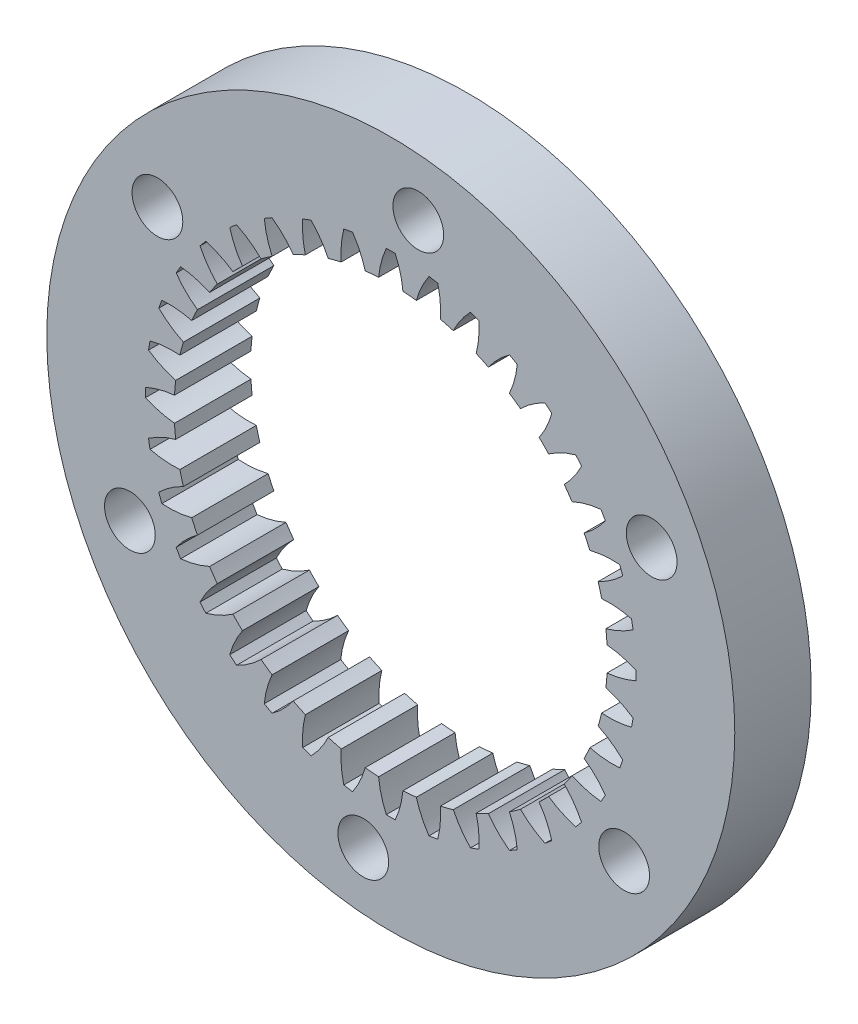
SolidWorks part; units mm, degrees
material "AISI 1020"
ref_plane "Front" through (0, 0, 0) normal (0, 0, 1) x (1, 0, 0)
ref_plane "Top" through (0, 0, 0) normal (0, 1, 0) x (1, 0, 0)
ref_plane "Right" through (0, 0, 0) normal (1, 0, 0) x (0, 0, -1)
sketch "Sketch2" plane through (0, 0, 0) normal (1, 0, 0) x (0, 0, -1)
  line L0 (0, 0) -> (-125.1835, 0) construction
  line L1 (-125.1835, 0) -> (0, 0) construction
ref_axis "Axis1" through (0, 0, -80.9) along (0, 0, 1)
sketch "gearSketch" plane through (0, 0, 0) normal (0, 0, 1) x (1, 0, 0)
  circle A0 centre (0, 0) radius 28.575
  dimension "bodyOD" = 57.15
extrude "gearBody" add sketch "gearSketch" along normal blind 6.35
sketch "boreSketch" plane through (0, 0, 0) normal (0, 0, -1) x (-1, 0, 0)
  circle A0 centre (0, 0) radius 17.9917
  dimension "minorDiameterBore" = 35.9833
extrude "bodyBore" cut sketch "boreSketch" against normal through all
sketch "toothCut1" plane through (-279.4, 0, 0) normal (0, 0, -1) x (-1, 0, 0)
  line L0 (-280.2309, 19.0319) -> (-272.8842, 17.2539) construction
  line L1 (-279.4, 0) -> (-279.4, 19.05) construction
  line L2 (-279.4, 0) -> (-280.2309, 19.0319) construction
  line L3 (-279.4, 279.4) -> (-279.4, 0) construction
  line L4 (-279.4, 0) -> (-280.4097, 17.9633)
  line L5 (-279.4, 0) -> (-278.3903, 17.9633)
  circle A0 centre (-279.4, 0) radius 17.9917 construction
  circle A1 centre (-279.4, 0) radius 18.4432 construction
  circle A2 centre (-279.4, 0) radius 19.05 construction
  arc A3 (-279.029, 20.3695) -> (-279.771, 20.3695) centre (-279.4, 0) ccw construction
  arc A4 (-279.029, 20.3695) -> (-278.3903, 17.9633) centre (-285.9158, 17.2539) cw
  arc A5 (-279.771, 20.3695) -> (-280.4097, 17.9633) centre (-272.8842, 17.2539) ccw
  arc A6 (-279.029, 20.3695) -> (-279.771, 20.3695) centre (-279.4, 0) ccw
  dimension "minorDiameter" = 35.9833
  dimension "baseDia" = 36.8864
  dimension "pd" = 38.1
  dimension "od" = 40.7458
  dimension "flankRadius2" = 7.5589
  dimension "toothAng" = 2.5
  dimension "flankRadius" = 7.5589
extrude "Cut-Extrude2" cut sketch "toothCut1" against normal through all
pattern_circular "CirPattern1" count 36 over 360 about axis through (0, 0, -80.9) along (0, 0, 1) of "Cut-Extrude2"
sketch "Sketch3" plane through (0, 0, 6.35) normal (0, 0, 1) x (1, 0, 0)
  circle A0 centre (2.286, 23.7025) radius 2.1082
  circle A1 centre (21.67, 9.8715) radius 2.1082
  circle A2 centre (19.384, -13.831) radius 2.1082
  circle A3 centre (-2.286, -23.7025) radius 2.1082
  circle A4 centre (-21.67, -9.8715) radius 2.1082
  circle A5 centre (-19.384, 13.831) radius 2.1082
  point P16 (0, 0)
  dimension "D1" = 23.8125
  dimension "D2" = 4.2164
  dimension "D4" = 2.286
  dimension "D5" = 0
  dimension "D3" = 6
extrude "Versakey" cut sketch "Sketch3" against normal through all
